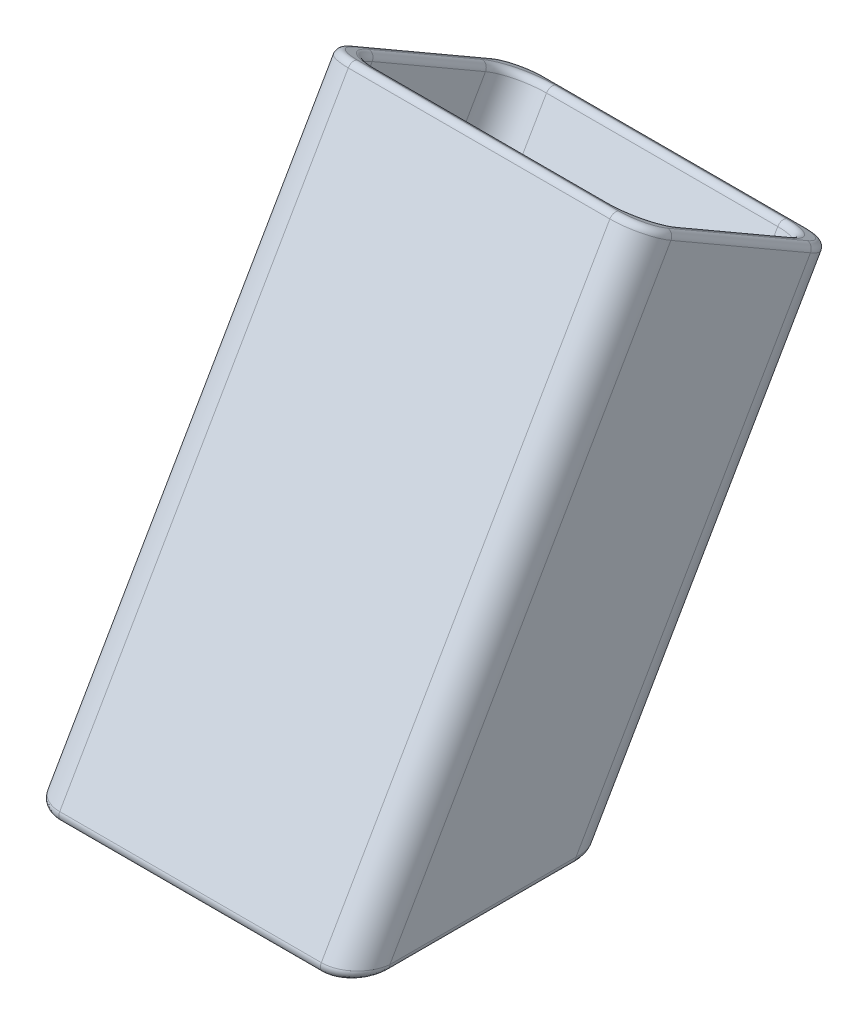
SolidWorks part; units mm, degrees
ref_plane "Front Plane" through (0, 0, 0) normal (0, 0, 1) x (1, 0, 0)
ref_plane "Top Plane" through (0, 0, 0) normal (0, 1, 0) x (1, 0, 0)
ref_plane "Right Plane" through (0, 0, 0) normal (1, 0, 0) x (0, 0, -1)
sketch "Sketch1" plane through (0, 0, 0) normal (1, 0, 0) x (0, 0, -1)
  line L0 (-20, 0) -> (25.4848, 78.782)
  line L1 (25.4848, 78.782) -> (55.4848, 61.4615)
  line L2 (55.4848, 61.4615) -> (20, 0)
  line L3 (20, 0) -> (-20, 0)
  line L4 (53.4752, 62.6218) -> (27.4944, 77.6218) construction
  line L5 (53.4752, 62.6218) -> (18.4752, 2) construction
  line L6 (27.4944, 77.6218) -> (-7.5056, 17) construction
  line L7 (18.4752, 2) -> (-7.5056, 17) construction
  point P2 (0, 0)
  point P5 (40.4848, 70.1218)
  point P7 (40.4848, 70.1218)
  point P10 (41.5756, 53.9386)
  point P13 (23.8727, 11.3487)
  dimension "D1" = 40
  dimension "D2" = 60
  dimension "D3" = 2
  dimension "D4" = 70
  dimension "D5" = 30
extrude "Boss-Extrude1" add sketch "Sketch1" along normal mid plane 50
sketch "Sketch2" plane through (0, 70.1218, -40.4848) normal (0, 0.866, -0.5) x (1, 0, 0)
  line L1 (-22.6795, -15) -> (22.6795, -15)
  line L2 (-22.6795, -15) -> (-22.6795, 15)
  line L3 (-22.6795, 15) -> (22.6795, 15)
  line L4 (22.6795, -15) -> (22.6795, 15)
  line L5 (-22.6795, -15) -> (22.6795, 15) construction
  line L6 (-22.6795, 15) -> (22.6795, -15) construction
  line L7 (25, 17.3205) -> (22.6795, 17.3205) construction
  line L8 (25, 17.3205) -> (25, 15) construction
  line L9 (25, 15) -> (22.6795, 15) construction
  line L10 (22.6795, 17.3205) -> (22.6795, 15) construction
  point P0 (0, 0)
  point P11 (22.6693, 14.7083)
extrude "Cut-Extrude1" cut sketch "Sketch2" against normal up to vertex (70 mm away) up to point (0, 2, -18.4752)
sketch "Sketch3" plane through (0, 9.5, -5.4848) normal (0, 0.866, -0.5) x (1, 0, 0)
  line L0 (-14.6795, 0) -> (14.6795, 0) construction
  line L1 (22.6795, -15) -> (22.6795, 15) construction
  point P4 (0, 0)
  dimension "D1" = 8
fillet "Fillet1" radius 5 8 edges at (-25, 30.7308, -37.7424) (25, 30.7308, -37.7424) (-25, 39.391, -2.7424) (25, 39.391, -2.7424) (22.6795, 47.3109, -9.9944) (-22.6795, 32.3109, -35.9752) (-22.6795, 47.3109, -9.9944) (22.6795, 32.3109, -35.9752)
fillet "Fillet2" radius 1 32 edges at (0, 78.782, -25.4848) (-23.5355, 78.0498, -26.7531) (-25, 70.1218, -40.4848) (-23.5355, 62.1938, -54.2166) (0, 61.4615, -55.4848) (23.5355, 62.1938, -54.2166) (25, 70.1218, -40.4848) (22.6795, 70.1218, -40.4848) (21.215, 63.354, -52.2069) (0, 62.6218, -53.4752) (-21.215, 63.354, -52.2069) (-22.6795, 70.1218, -40.4848) (-21.215, 76.8895, -28.7627) (0, 77.6218, -27.4944) (-21.215, 16.2678, 6.2373) (-22.6795, 9.5, -5.4848) (-21.215, 2.7322, -17.2069) (0, 2, -18.4752) (21.215, 2.7322, -17.2069) (22.6795, 9.5, -5.4848) (21.215, 16.2678, 6.2373) (23.5355, 78.0498, -26.7531) (21.215, 76.8895, -28.7627) (0, 17, 7.5056) (25, 0, 0) (23.5355, 0, -18.309) (0, 0, -20) (-23.5355, 0, -18.309) (-25, 0, 0) (-23.5355, 0, 18.309) (0, 0, 20) (23.5355, 0, 18.309)
hole_wizard "CSK for M5 Flat Head Machine Screw1" positions "Sketch4" profile "Sketch5" countersink size "M5" standard "ANSI Metric" end condition through all
sketch "Sketch4" plane through (0, 9.5, -5.4848) normal (0, 0.866, -0.5) x (1, 0, 0)
  point P0 (-14.6795, 0)
  point P3 (14.6795, 0)
sketch "Sketch5" plane through (-14.6795, 9.5, -5.4848) normal (1, 0, 0) x (0, 0.5, 0.866)
  line L0 (0, 0) -> (0, 20.6036)
  line L1 (0, 20.6036) -> (2.9, 20.6036)
  line L2 (2.9, 20.6036) -> (2.9, 2.3)
  line L3 (2.9, 2.3) -> (5.2, 0)
  line L5 (5.2, 0) -> (0, 0)
  line L6 (-2.9, 2.3) -> (-5.2, 0) construction
  line L11 (0, -6.35) -> (0, 107.95) construction
  dimension "Thru Hole Dia." = 5.8
  dimension "Thru Hole Depth" = 20.6036
  dimension "Near C'Sink Dia." = 10.4
  dimension "Near C'Sink Angle" = 90
